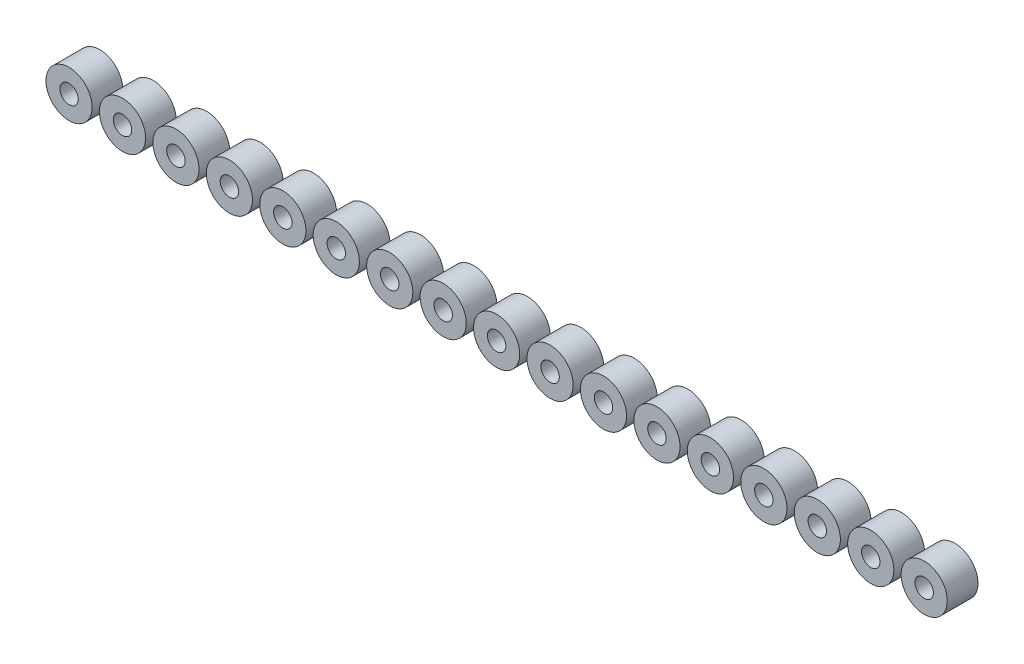
SolidWorks part; units mm, degrees
ref_plane "Płaszczyzna przednia" through (0, 0, 0) normal (0, 0, 1) x (1, 0, 0)
ref_plane "Płaszczyzna górna" through (0, 0, 0) normal (0, 1, 0) x (1, 0, 0)
ref_plane "Płaszczyzna prawa" through (0, 0, 0) normal (1, 0, 0) x (0, 0, -1)
sketch "Szkic1" plane through (0, 0, 0) normal (0, 0, 1) x (1, 0, 0)
  circle A0 centre (0, 0) radius 381
  circle A1 centre (0, 0) radius 953
  circle A2 centre (2206, 0) radius 953
  circle A3 centre (2206, 0) radius 381
  circle A4 centre (4412, 0) radius 953
  circle A5 centre (4412, 0) radius 381
  circle A6 centre (6618, 0) radius 953
  circle A7 centre (6618, 0) radius 381
  circle A8 centre (8824, 0) radius 953
  circle A9 centre (8824, 0) radius 381
  circle A10 centre (11030, 0) radius 953
  circle A11 centre (11030, 0) radius 381
  circle A12 centre (13236, 0) radius 953
  circle A13 centre (13236, 0) radius 381
  circle A14 centre (15442, 0) radius 953
  circle A15 centre (15442, 0) radius 381
  circle A16 centre (17648, 0) radius 953
  circle A17 centre (17648, 0) radius 381
  circle A18 centre (19854, 0) radius 953
  circle A19 centre (19854, 0) radius 381
  circle A20 centre (22060, 0) radius 953
  circle A21 centre (22060, 0) radius 381
  circle A22 centre (24266, 0) radius 953
  circle A23 centre (24266, 0) radius 381
  circle A24 centre (26472, 0) radius 953
  circle A25 centre (26472, 0) radius 381
  circle A26 centre (28678, 0) radius 953
  circle A27 centre (28678, 0) radius 381
  circle A28 centre (30884, 0) radius 953
  circle A29 centre (30884, 0) radius 381
  circle A30 centre (33090, 0) radius 953
  circle A31 centre (33090, 0) radius 381
  circle A32 centre (35296, 0) radius 953
  circle A33 centre (35296, 0) radius 381
  dimension "D1" = 762
  dimension "D2" = 1906
  dimension "D4" = 2206
  dimension "D3" = 17
extrude "Dodanie-wyciągnięcie1" add sketch "Szkic1" along normal blind 1268
ref_axis "Oś1" through (0, 0, 1268) along (0, 0, -1)
ref_axis "Oś2" through (2206, 0, 1268) along (0, 0, -1)
ref_axis "Oś3" through (4412, 0, 1268) along (0, 0, -1)
ref_axis "Oś4" through (6618, 0, 1268) along (0, 0, -1)
ref_axis "Oś5" through (8824, 0, 1268) along (0, 0, -1)
ref_axis "Oś6" through (11030, 0, 1268) along (0, 0, -1)
ref_axis "Oś7" through (13236, 0, 1268) along (0, 0, -1)
ref_axis "Oś8" through (15442, 0, 1268) along (0, 0, -1)
ref_axis "Oś9" through (17648, 0, 1268) along (0, 0, -1)
ref_axis "Oś10" through (19854, 0, 1268) along (0, 0, -1)
ref_axis "Oś11" through (22060, 0, 1268) along (0, 0, -1)
ref_axis "Oś12" through (24266, 0, 1268) along (0, 0, -1)
ref_axis "Oś13" through (26472, 0, 1268) along (0, 0, -1)
ref_axis "Oś14" through (28678, 0, 1268) along (0, 0, -1)
ref_axis "Oś15" through (30884, 0, 1268) along (0, 0, -1)
ref_axis "Oś16" through (33090, 0, 1268) along (0, 0, -1)
ref_axis "Oś17" through (35296, 0, 1268) along (0, 0, -1)
equation "\"D4@Szkic1\"=\"D2@Szkic1\"+300mm"
